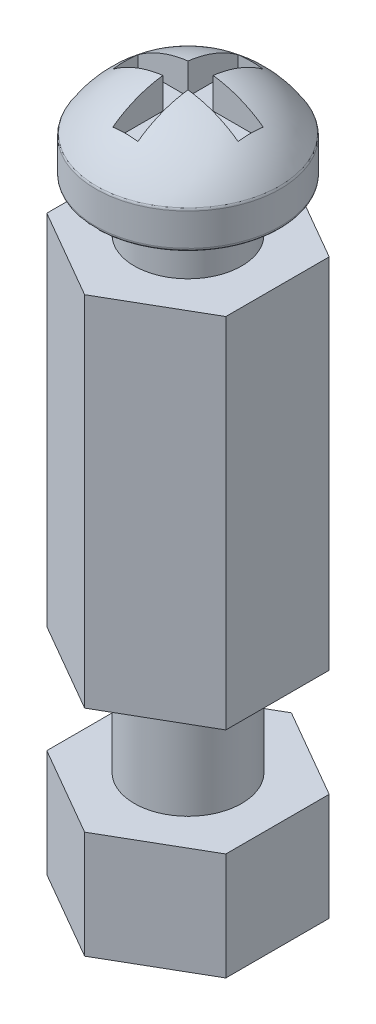
SolidWorks part; units mm, degrees
ref_plane "Front Plane" through (0, 0, 0) normal (0, 0, 1) x (1, 0, 0)
ref_plane "Top Plane" through (0, 0, 0) normal (0, 1, 0) x (1, 0, 0)
ref_plane "Right Plane" through (0, 0, 0) normal (1, 0, 0) x (0, 0, -1)
sketch "Sketch1" plane through (0, 0, 0) normal (0, 1, 0) x (1, 0, 0)
  line L1 (2.5, 1.4434) -> (0, 2.8868)
  line L2 (0, 2.8868) -> (-2.5, 1.4434)
  line L3 (-2.5, 1.4434) -> (-2.5, -1.4434)
  line L4 (-2.5, -1.4434) -> (0, -2.8868)
  line L5 (0, -2.8868) -> (2.5, -1.4434)
  line L6 (2.5, -1.4434) -> (2.5, 1.4434)
  circle A0 centre (0, 0) radius 2.5 construction
  circle A1 centre (0, 0) radius 1.5
  dimension "D1" = 3
  dimension "D2" = 5
extrude "Boss-Extrude1" add sketch "Sketch1" along normal blind 10 contours A1 | L5 L6 L1 L2 L3 L4 A1 region at (2.4236, 0, 0) region at (0, 0, 0)
extrude "Boss-Extrude2" add sketch "Sketch1<4>" against normal blind 6 contours A1 region at (0, 0, 0)
sketch "Sketch1<4>" plane through (0, 0, 0) normal (0, 1, 0) x (1, 0, 0) same geometry as "Sketch1"
sketch "Sketch3" plane through (0, 0, 0) normal (0, 0, 1) x (1, 0, 0)
  line L0 (1.5, -6) -> (1.5, 0) construction
  line L1 (0, 10) -> (1.5, 10)
  line L2 (0, 10) -> (0, 11.4)
  line L3 (0, 11.4) -> (1.5, 11.4)
  line L4 (1.5, 10) -> (1.5, 11.4)
  line L5 (0, 10) -> (0, 0) construction
  line L6 (1.5, 11.4) -> (3.6588, 11.4)
  line L7 (0, 11.4) -> (0, 13.9)
  line L8 (0, 10) -> (0, -6) construction
  line L9 (-1.5, -6) -> (1.5, -6) construction
  line L10 (0, 2) -> (3.9182, 2) construction
  line L11 (0, -7.4) -> (0, -9.9)
  line L12 (1.5, -7.4) -> (3.6588, -7.4)
  line L13 (1.5, -6) -> (1.5, -7.4)
  line L14 (0, -7.4) -> (1.5, -7.4)
  line L15 (0, -6) -> (0, -7.4)
  line L16 (0, -6) -> (1.5, -6)
  line L17 (2.5777, 12.4) -> (2.5777, 11.4)
  circle A0 centre (0, 10.9) radius 3
  circle A1 centre (2.4527, 12.4) radius 0.125
  circle A2 centre (0, -6.9) radius 3
  circle A3 centre (2.4527, -8.4) radius 0.125
  dimension "D2" = 0.25
  dimension "D4" = 6
  dimension "D1" = 1.4
  dimension "D3" = 1
  dimension "D5" = 0.5
revolve "Revolve1" add sketch "Sketch3" angle 360 about L8 region at (0.75, 10.7, 0) region at (1.1363, 12.4777, 0) region at (2.4527, 12.4, 0)
ref_plane "Plane1" through (0, 20, 0) normal (0, 1, 0) x (1, 0, 0)
sketch "Sketch4" plane through (0, 20, 0) normal (0, 1, 0) x (1, 0, 0)
  line L1 (-1.75, -0.35) -> (1.75, -0.35)
  line L2 (-1.75, -0.35) -> (-1.75, 0.35)
  line L3 (-1.75, 0.35) -> (1.75, 0.35)
  line L4 (1.75, -0.35) -> (1.75, 0.35)
  line L5 (-1.75, -0.35) -> (1.75, 0.35) construction
  line L6 (-1.75, 0.35) -> (1.75, -0.35) construction
  line L7 (-0.35, -1.75) -> (0.35, -1.75)
  line L8 (-0.35, -1.75) -> (-0.35, 1.75)
  line L9 (-0.35, 1.75) -> (0.35, 1.75)
  line L10 (0.35, -1.75) -> (0.35, 1.75)
  line L11 (-0.35, -1.75) -> (0.35, 1.75) construction
  line L12 (-0.35, 1.75) -> (0.35, -1.75) construction
  point P0 (0, 0)
  point P6 (0, 0)
  dimension "D1" = 0.7
  dimension "D2" = 3.5
extrude "Cut-Extrude1" cut sketch "Sketch4" against normal blind 7 contours L7 L10 L1 L8 | L10 L1 L4 L3 | L3 L10 L9 L8 | L1 L8 L3 L2 | L1 L10 L3 L8 region at (-1.05, 20, 0) region at (0, 20, 0) region at (0, 20, 1.05) region at (1.05, 20, 0) region at (0, 20, -1.05)
fillet "Fillet1" radius 0.1 1 edges at (-2.5777, 11.4, 0)
sketch "Sketch5" plane through (0, -6, 0) normal (0, -1, 0) x (1, 0, 0)
  line L6 (2.5, 1.4434) -> (0, 2.8868)
  line L7 (0, 2.8868) -> (-2.5, 1.4434)
  line L8 (-2.5, 1.4434) -> (-2.5, -1.4434)
  line L9 (-2.5, -1.4434) -> (0, -2.8868)
  line L10 (0, -2.8868) -> (2.5, -1.4434)
  line L11 (2.5, -1.4434) -> (2.5, 1.4434)
  line L12 (2.5, 1.4434) -> (0, 2.8868)
  line L13 (0, 2.8868) -> (-2.5, 1.4434)
  line L14 (-2.5, 1.4434) -> (-2.5, -1.4434)
  line L15 (-2.5, -1.4434) -> (0, -2.8868)
  line L16 (0, -2.8868) -> (2.5, -1.4434)
  line L17 (2.5, -1.4434) -> (2.5, 1.4434)
  circle A0 centre (0, 0) radius 1.5 construction
  circle A1 centre (0, 0) radius 1.5
  dimension "D1" = 0
extrude "Boss-Extrude3" add sketch "Sketch5" against normal blind 3 separate body
